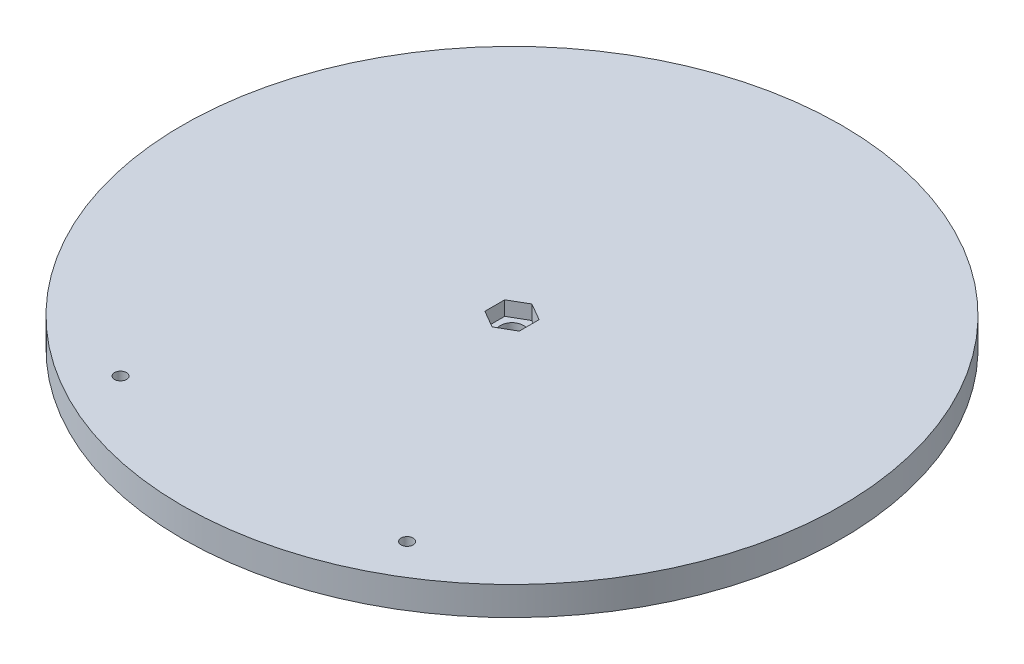
SolidWorks part; units mm, degrees
ref_plane "前视基准面" through (0, 0, 0) normal (0, 0, 1) x (1, 0, 0)
ref_plane "上视基准面" through (0, 0, 0) normal (0, 1, 0) x (1, 0, 0)
ref_plane "右视基准面" through (0, 0, 0) normal (1, 0, 0) x (0, 0, -1)
sketch "草图2" plane through (0, 0, 0) normal (0, 1, 0) x (1, 0, 0)
  line L1 (4, -2.3094) -> (4, 2.3094)
  line L2 (4, 2.3094) -> (0, 4.6188)
  line L3 (0, 4.6188) -> (-4, 2.3094)
  line L4 (-4, 2.3094) -> (-4, -2.3094)
  line L5 (-4, -2.3094) -> (0, -4.6188)
  line L6 (0, -4.6188) -> (4, -2.3094)
  line L7 (6, -3.4641) -> (6, 3.4641)
  line L8 (6, 3.4641) -> (0, 6.9282)
  line L9 (0, 6.9282) -> (-6, 3.4641)
  line L10 (-6, 3.4641) -> (-6, -3.4641)
  line L11 (-6, -3.4641) -> (0, -6.9282)
  line L12 (0, -6.9282) -> (6, -3.4641)
  circle A0 centre (0, 0) radius 115
  circle A1 centre (0, 0) radius 4 construction
  circle A2 centre (0, 0) radius 6 construction
  circle A3 centre (0, 0) radius 4
  point P3 (4, 0)
  dimension "D1" = 230
  dimension "D2" = 8
  dimension "D3" = 2
extrude "凸台-拉伸2" add sketch "草图2" along normal blind 10 contours A0 L12 L11 L10 L9 L8 L7 region at (-111.7473, 0, 0)
extrude "凸台-拉伸3" add sketch "草图2<4>" along normal blind 5 contours L11 L12 L7 L8 L9 L10 L6 L5 L4 L3 L2 L1 | L1 L2 L3 L4 L5 L6 region at (2.9083, 0, 5.0374)
sketch "草图2<4>" plane through (0, 0, 0) normal (0, 1, 0) x (1, 0, 0) same geometry as "草图2"
extrude "切除-拉伸2" cut sketch "草图2<6>" along normal up to next contours A3 region at (0, 0, 0)
sketch "草图2<6>" plane through (0, 0, 0) normal (0, 1, 0) x (1, 0, 0) same geometry as "草图2"
sketch "草图4" plane through (0, 10, 0) normal (0, 1, 0) x (1, 0, 0)
  line L0 (0, 115) -> (0, -115) construction
  circle A0 centre (-50, -86.6025) radius 2.1
  circle A2 centre (0, 0) radius 115 construction
  circle A3 centre (50, -86.6025) radius 2.1
  dimension "D1" = 4.2
  dimension "D2" = 50
  dimension "D3" = 100
extrude "切除-拉伸3" cut sketch "草图4" against normal up to next contours A3 | A0
